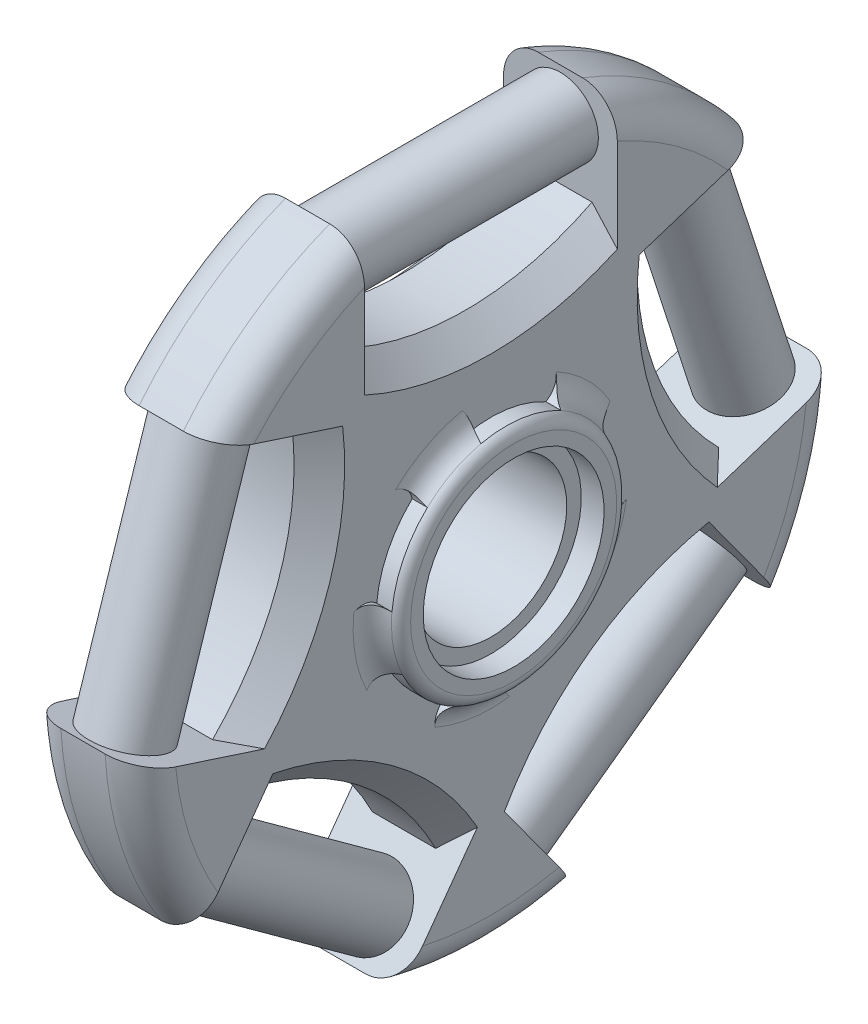
SolidWorks part; units mm, degrees
ref_plane "Front Plane" through (0, 0, 0) normal (0, 0, 1) x (1, 0, 0)
ref_plane "Top Plane" through (0, 0, 0) normal (0, 1, 0) x (1, 0, 0)
ref_plane "Right Plane" through (0, 0, 0) normal (1, 0, 0) x (0, 0, -1)
sketch "Sketch1" plane through (0, 0, 0) normal (1, 0, 0) x (0, 0, -1)
  line L0 (32.8598, 21.1914) -> (13.8386, 15.0111)
  line L1 (-10, 37.8) -> (10, 37.8)
  line L2 (-10, 37.8) -> (-10, 17.8)
  line L4 (10, 37.8) -> (10, 17.8)
  line L5 (-10, 37.8) -> (10, 17.8) construction
  line L6 (-10, 17.8) -> (10, 37.8) construction
  line L7 (39.0401, 2.1703) -> (20.019, -4.0101)
  line L8 (32.8598, 21.1914) -> (39.0401, 2.1703)
  line L9 (30.3085, -24.703) -> (18.5527, -8.5226)
  line L10 (14.1281, -36.4587) -> (2.3724, -20.2784)
  line L11 (30.3085, -24.703) -> (14.1281, -36.4587)
  line L12 (-14.1281, -36.4587) -> (-2.3724, -20.2784)
  line L13 (-30.3085, -24.703) -> (-18.5527, -8.5226)
  line L14 (-14.1281, -36.4587) -> (-30.3085, -24.703)
  line L15 (-39.0401, 2.1703) -> (-20.019, -4.0101)
  line L16 (-32.8598, 21.1914) -> (-13.8386, 15.0111)
  line L17 (-39.0401, 2.1703) -> (-32.8598, 21.1914)
  circle A0 centre (0, 0) radius 27.8
  arc A1 (-10, 17.8) -> (10, 17.8) centre (0, 37.3959) ccw
  arc A2 (13.8386, 15.0111) -> (20.019, -4.0101) centre (35.5656, 11.556) ccw
  arc A3 (18.5527, -8.5226) -> (2.3724, -20.2784) centre (21.9808, -30.2539) ccw
  arc A4 (-2.3724, -20.2784) -> (-18.5527, -8.5226) centre (-21.9808, -30.2539) ccw
  arc A5 (-20.019, -4.0101) -> (-13.8386, 15.0111) centre (-35.5656, 11.556) ccw
  circle A6 centre (0, 0) radius 6
  point P3 (0, 27.8)
  point P31 (0, 0)
  dimension "D1" = 55.6
  dimension "D4" = 22
  dimension "D6" = 12
  dimension "D2" = 20
  dimension "D3" = 20
  dimension "D5" = 5
extrude "Boss-Extrude2" add sketch "Sketch1" along normal blind 9 contours A5 L15 A0 L13 A4 L12 L10 A3 L9 L7 A2 L0 L4 A1 L2 L16 A6 region at (0, 17.0035, -17.4703)
fillet "Fillet1" radius 2.75 10 edges at (0, -8.5907, 26.4394) (9, -8.5907, 26.4394) (9, -27.8, 0) (0, -27.8, 0) (9, -8.5907, -26.4394) (0, -8.5907, -26.4394) (0, 22.4907, -16.3404) (9, 22.4907, -16.3404) (9, 22.4907, 16.3404) (0, 22.4907, 16.3404)
sketch "Sketch3" plane through (0, 0, 0) normal (-1, 0, 0) x (0, 0, 1)
  circle A0 centre (0, 0) radius 7.15
  circle A1 centre (0, 0) radius 9.15
  dimension "D1" = 14.3
  dimension "D2" = 18.3
extrude "Boss-Extrude3" add sketch "Sketch3" along normal blind 1.8 and the other way blind 10.8
chamfer "Chamfer2" distance 2 angle 45 10 edges at (9, -12.4556, -9.0495) (9, 4.7576, -14.6424) (9, -12.4556, 9.0495) (9, 4.7576, 14.6424) (9, 15.3959, 0) (0, 4.7576, 14.6424) (0, -12.4556, 9.0495) (0, -12.4556, -9.0495) (0, 4.7576, -14.6424) (0, 15.3959, 0)
fillet "Fillet3" radius 1 2 edges at (10.8, 0, 9.15) (-1.8, 0, 9.15)
fillet "Fillet4" radius 2 2 edges at (0, 0, -9.15) (9, 0, -9.15)
sketch "Sketch5" plane through (0, 0, 0) normal (-1, 0, 0) x (0, 0, 1)
  line L0 (6.2981, -6.5219) -> (7.5715, -7.8405) construction
  line L1 (0, 0) -> (4.168, -4.316) construction
  line L2 (0, 0) -> (6, 0) construction
  arc A0 (9.8091, -4.7521) -> (4.4069, -9.9689) centre (0, 0) cw
  circle A1 centre (0, 0) radius 10.8995 construction
  arc A2 (8.1947, -3.8793) -> (3.5909, -8.3251) centre (0, 0) cw
  circle A3 centre (0, 0) radius 9.0665 construction
  arc A4 (3.5909, -8.3251) -> (4.4069, -9.9689) centre (2.8248, -9.7298) cw
  arc A5 (8.1947, -3.8793) -> (9.8091, -4.7521) centre (8.3785, -5.4687) cw
  circle A6 centre (0, 0) radius 6 construction
  arc A7 (-1.1571, -8.9924) -> (-1.4883, -10.7975) centre (-2.6119, -9.6583) cw
  arc A8 (-1.4883, -10.7975) -> (-8.1192, -7.2717) centre (0, 0) cw
  arc A9 (-6.808, -5.9878) -> (-8.1192, -7.2717) centre (-8.3806, -5.6932) cw
  arc A10 (-1.1571, -8.9924) -> (-6.808, -5.9878) centre (0, 0) cw
  arc A11 (-8.9098, -1.6783) -> (-10.7289, -1.9211) centre (-9.9928, -0.5005) cw
  arc A12 (-10.7289, -1.9211) -> (-9.4248, 5.4747) centre (0, 0) cw
  arc A13 (-7.7985, 4.6244) -> (-9.4248, 5.4747) centre (-8.0044, 6.2111) cw
  arc A14 (-8.9098, -1.6783) -> (-7.7985, 4.6244) centre (0, 0) cw
  arc A15 (-4.3495, 7.9551) -> (-5.1425, 9.6101) centre (-3.5639, 9.349) cw
  arc A16 (-5.1425, 9.6101) -> (2.2944, 10.6553) centre (0, 0) cw
  arc A17 (1.9882, 8.8458) -> (2.2944, 10.6553) centre (3.4337, 9.5319) cw
  arc A18 (-4.3495, 7.9551) -> (1.9882, 8.8458) centre (0, 0) cw
  arc A19 (6.2217, 6.5949) -> (7.5507, 7.8605) centre (7.7901, 6.2785) cw
  arc A20 (7.5507, 7.8605) -> (10.8428, 1.1106) centre (0, 0) cw
  arc A21 (9.0273, 0.8426) -> (10.8428, 1.1106) centre (10.1265, -0.3201) cw
  arc A22 (6.2217, 6.5949) -> (9.0273, 0.8426) centre (0, 0) cw
  point P45 (0, 0)
  dimension "D2" = 1.6
  dimension "D1" = 46
  dimension "D3" = 7
  dimension "D4" = 6.4
  dimension "D5" = 5
extrude "Cut-Extrude1" cut sketch "Sketch5" along normal blind 1.8
ref_plane "Plane2" through (4.5, 0, 0) normal (1, 0, 0) x (0, 0, -1)
mirror "Mirror1" about plane through (4.5, 0, 0) normal (1, 0, 0) of "Cut-Extrude1"
sketch "Sketch6" plane through (0, -5.8779, -8.0902) normal (0, 0.5878, 0.809) x (1, 0, 0)
  line L3 (6.25, -25.9392) -> (2.75, -25.9392) construction
  line L4 (9, -22.9674) -> (9, -15.5785) construction
  circle A0 centre (4.5, -22.4392) radius 3
  dimension "D1" = 6
  dimension "D2" = 3.5
  dimension "D3" = 4.5
extrude "Boss-Extrude4" add sketch "Sketch6" along normal up to surface (20 mm away) up to face at (4.3028, -10.9073, 20.2853)
sketch "Sketch7" plane through (0, -9.5106, 3.0902) normal (0, 0.9511, -0.309) x (1, 0, 0)
  line L1 (6.25, -25.9392) -> (2.75, -25.9392) construction
  line L2 (0, -22.9674) -> (0, -15.5785) construction
  circle A0 centre (4.5, -22.4392) radius 3
  dimension "D1" = 6
  dimension "D2" = 3.5
  dimension "D3" = 4.5
extrude "Boss-Extrude5" add sketch "Sketch7" along normal up to surface (20 mm away) up to face at (4.3028, 15.9219, 16.6419)
sketch "Sketch8" plane through (0, 0, -10) normal (0, 0, 1) x (1, 0, 0)
  line L0 (9, 22.9674) -> (9, 15.5785) construction
  line L1 (6.25, 25.9392) -> (2.75, 25.9392) construction
  circle A0 centre (4.5, 22.4392) radius 3
  dimension "D1" = 6
  dimension "D2" = 4.5
  dimension "D3" = 3.5
extrude "Boss-Extrude6" add sketch "Sketch8" along normal up to surface (20 mm away) contours A0 up to face at (4.6972, 20.7476, 10)
sketch "Sketch9" plane through (0, -5.8779, 8.0902) normal (0, 0.5878, -0.809) x (-1, 0, 0)
  line L0 (-6.25, -25.9392) -> (-2.75, -25.9392) construction
  line L1 (-9, -22.9674) -> (-9, -15.5785) construction
  circle A0 centre (-4.5, -22.4392) radius 3
  dimension "D1" = 6
  dimension "D2" = 3.5
  dimension "D3" = 4.5
extrude "Boss-Extrude7" add sketch "Sketch9" along normal up to surface (20 mm away) up to face at (4.6972, -10.9073, -20.2853)
sketch "Sketch10" plane through (0, -9.5106, -3.0902) normal (0, 0.9511, 0.309) x (1, 0, 0)
  line L1 (6.25, 25.9392) -> (2.75, 25.9392) construction
  line L2 (9, 22.9674) -> (9, 15.5785) construction
  circle A0 centre (4.5, 22.4392) radius 3
  dimension "D1" = 6
  dimension "D2" = 3.5
  dimension "D3" = 4.5
extrude "Boss-Extrude8" add sketch "Sketch10" along normal up to surface (20 mm away) up to face at (4.6972, 15.9219, -16.6419)
